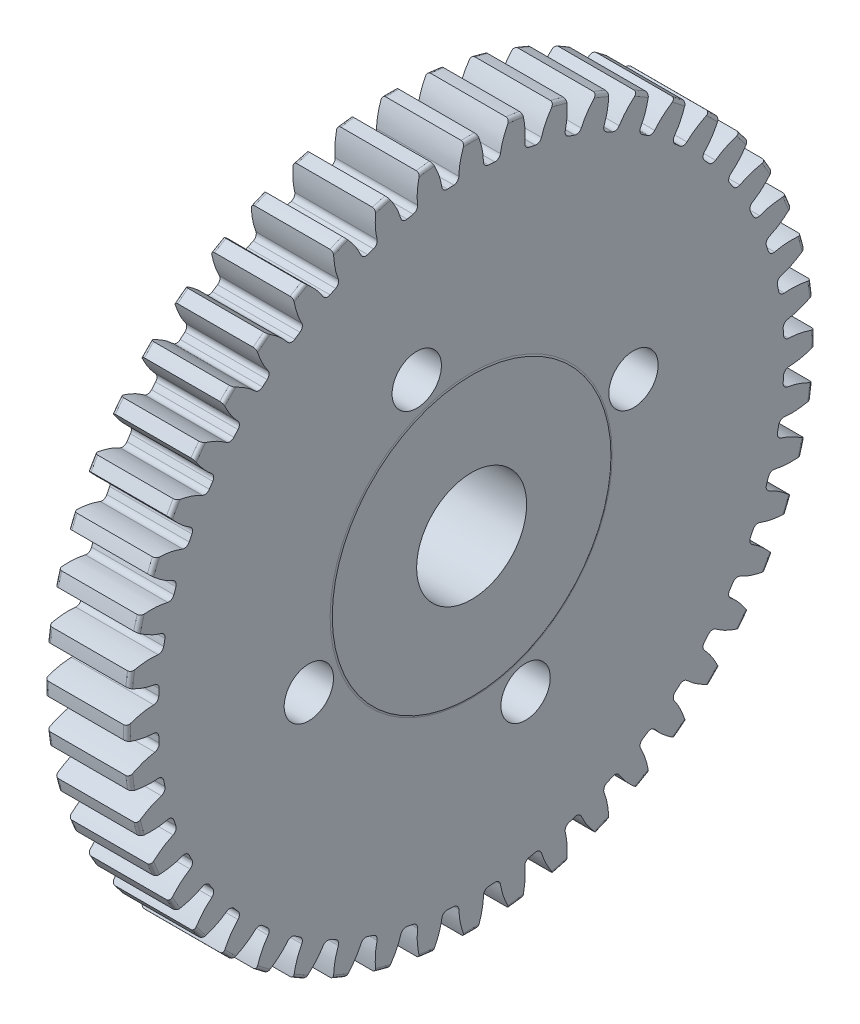
SolidWorks part; units mm, degrees
material "Delrin 2700 NC010, Low Viscosity Acetal Copolymer (SS)"
ref_plane "Front Plane" through (0, 0, 0) normal (0, 0, 1) x (1, 0, 0)
ref_plane "Top Plane" through (0, 0, 0) normal (0, 1, 0) x (1, 0, 0)
ref_plane "Right Plane" through (0, 0, 0) normal (1, 0, 0) x (0, 0, -1)
sketch "Sketch1" plane through (0, 0, 0) normal (0, 0, 1) x (1, 0, 0)
  line L0 (-2.3749, 19.8438) -> (-2.3749, 0)
  line L1 (-2.3749, 0) -> (2.3749, 0)
  line L2 (2.3749, 0) -> (2.3749, 19.8438)
  line L3 (2.3749, 19.8438) -> (-2.3749, 19.8438)
  line L4 (-2.3749, 0) -> (2.3749, 0) construction
revolve "Revolve1" add sketch "Sketch1" angle 360 about L4 reverse direction yes
sketch "Sketch2" plane through (-2.3749, 0, 0) normal (-1, 0, 0) x (0, 0, 1)
  arc A0 (0.7316, 18.0319) -> (1.6283, 17.9731) centre (0, 0) cw
  arc A1 (2.2123, 19.72) -> (0.3806, 19.8401) centre (0, 0) ccw
  spline S0 degree 3 poles (0.3806, 19.8401) (0.4054, 19.7738) (0.4294, 19.7071) (0.4523, 19.6401) (0.5249, 19.4282) (0.5865, 19.212) (0.6329, 18.9928) (0.6803, 18.7688) (0.6967, 18.5388) (0.7099, 18.3101) (0.7153, 18.2172) (0.7242, 18.1246) (0.7316, 18.0319) knots -0.000212 -0.000212 -0.000212 -0.000212 0 0 0 0.000672 0.000672 0.000672 0.001361 0.001361 0.001361 0.00164 0.00164 0.00164 0.00164
  spline S1 degree 3 poles (1.6283, 17.9731) (1.6477, 18.0641) (1.6686, 18.1548) (1.6861, 18.2461) (1.7281, 18.4663) (1.7727, 18.6874) (1.8467, 18.8989) (1.9223, 19.115) (2.0133, 19.326) (2.1151, 19.5311) (2.1466, 19.5946) (2.179, 19.6575) (2.2123, 19.72) knots -0.000279 -0.000279 -0.000279 -0.000279 0 0 0 0.000672 0.000672 0.000672 0.001357 0.001357 0.001357 0.001569 0.001569 0.001569 0.001569
extrude "Cut-Extrude1" cut sketch "Sketch2" against normal through all
sketch "Sketch3" plane through (-2.3749, 0, 0) normal (-1, 0, 0) x (0, 0, 1)
  arc A0 (3.079, 17.7821) -> (3.9603, 17.6068) centre (0, 0) cw
  arc A1 (4.7674, 19.2626) -> (2.967, 19.6207) centre (0, 0) ccw
  spline S0 degree 3 poles (2.967, 19.6207) (2.983, 19.5517) (2.998, 19.4825) (3.012, 19.413) (3.0562, 19.1935) (3.0891, 18.9711) (3.1065, 18.7477) (3.1243, 18.5194) (3.1106, 18.2892) (3.0938, 18.0608) (3.087, 17.968) (3.0838, 17.875) (3.079, 17.7821) knots -0.000212 -0.000212 -0.000212 -0.000212 0 0 0 0.000672 0.000672 0.000672 0.001361 0.001361 0.001361 0.00164 0.00164 0.00164 0.00164
  spline S1 degree 3 poles (3.9603, 17.6068) (3.9914, 17.6945) (4.024, 17.7816) (4.0533, 17.87) (4.1236, 18.0827) (4.1967, 18.2962) (4.2977, 18.4962) (4.4008, 18.7006) (4.5187, 18.8979) (4.6463, 19.088) (4.6858, 19.1467) (4.7262, 19.2049) (4.7674, 19.2626) knots -0.000279 -0.000279 -0.000279 -0.000279 0 0 0 0.000672 0.000672 0.000672 0.001357 0.001357 0.001357 0.001569 0.001569 0.001569 0.001569
extrude "Cut-Extrude2" cut sketch "Sketch3" against normal through all
sketch "Sketch4" plane through (-2.3749, 0, 0) normal (-1, 0, 0) x (0, 0, 1)
  arc A0 (5.3737, 17.2281) -> (6.2246, 16.9392) centre (0, 0) cw
  arc A1 (7.2408, 18.4755) -> (5.5026, 19.0656) centre (0, 0) ccw
  spline S0 degree 3 poles (5.5026, 19.0656) (5.5094, 18.9951) (5.5153, 18.9245) (5.5201, 18.8538) (5.5354, 18.6303) (5.5389, 18.4055) (5.527, 18.1819) (5.5148, 17.9532) (5.4712, 17.7267) (5.4248, 17.5025) (5.4059, 17.4114) (5.3906, 17.3196) (5.3737, 17.2281) knots -0.000212 -0.000212 -0.000212 -0.000212 0 0 0 0.000672 0.000672 0.000672 0.001361 0.001361 0.001361 0.00164 0.00164 0.00164 0.00164
  spline S1 degree 3 poles (6.2246, 16.9392) (6.2669, 17.0221) (6.3106, 17.1043) (6.3511, 17.188) (6.4486, 17.3898) (6.5489, 17.5918) (6.6752, 17.777) (6.8041, 17.9662) (6.9467, 18.1464) (7.0981, 18.3182) (7.1449, 18.3713) (7.1925, 18.4237) (7.2408, 18.4755) knots -0.000279 -0.000279 -0.000279 -0.000279 0 0 0 0.000672 0.000672 0.000672 0.001357 0.001357 0.001357 0.001569 0.001569 0.001569 0.001569
extrude "Cut-Extrude3" cut sketch "Sketch4" against normal through all
sketch "Sketch5" plane through (-2.3749, 0, 0) normal (-1, 0, 0) x (0, 0, 1)
  arc A0 (7.5764, 16.3793) -> (8.3824, 15.9819) centre (0, 0) cw
  arc A1 (9.5904, 17.3723) -> (7.9441, 18.1842) centre (0, 0) ccw
  spline S0 degree 3 poles (7.9441, 18.1842) (7.9417, 18.1134) (7.9383, 18.0427) (7.9338, 17.972) (7.9197, 17.7484) (7.894, 17.5251) (7.8529, 17.3049) (7.811, 17.0798) (7.7382, 16.8609) (7.6629, 16.6447) (7.6323, 16.5568) (7.6051, 16.4678) (7.5764, 16.3793) knots -0.000212 -0.000212 -0.000212 -0.000212 0 0 0 0.000672 0.000672 0.000672 0.001361 0.001361 0.001361 0.00164 0.00164 0.00164 0.00164
  spline S1 degree 3 poles (8.3824, 15.9819) (8.4351, 16.0585) (8.4892, 16.1342) (8.5402, 16.212) (8.6633, 16.3993) (8.7891, 16.5865) (8.9384, 16.7536) (9.091, 16.9244) (9.2558, 17.0845) (9.4283, 17.235) (9.4817, 17.2816) (9.5358, 17.3273) (9.5904, 17.3723) knots -0.000279 -0.000279 -0.000279 -0.000279 0 0 0 0.000672 0.000672 0.000672 0.001357 0.001357 0.001357 0.001569 0.001569 0.001569 0.001569
extrude "Cut-Extrude4" cut sketch "Sketch5" against normal through all
sketch "Sketch6" plane through (-2.3749, 0, 0) normal (-1, 0, 0) x (0, 0, 1)
  arc A0 (9.6495, 15.2503) -> (10.3967, 14.751) centre (0, 0) cw
  arc A1 (11.7759, 15.9719) -> (10.2497, 16.9917) centre (0, 0) ccw
  spline S0 degree 3 poles (10.2497, 16.9917) (10.238, 16.9219) (10.2254, 16.8522) (10.2118, 16.7827) (10.1686, 16.5629) (10.1139, 16.3448) (10.0445, 16.1318) (9.9735, 15.9141) (9.8728, 15.7067) (9.7699, 15.5021) (9.7281, 15.4189) (9.6895, 15.3342) (9.6495, 15.2503) knots -0.000212 -0.000212 -0.000212 -0.000212 0 0 0 0.000672 0.000672 0.000672 0.001361 0.001361 0.001361 0.00164 0.00164 0.00164 0.00164
  spline S1 degree 3 poles (10.3967, 14.751) (10.459, 14.8201) (10.5225, 14.8882) (10.5833, 14.9586) (10.7297, 15.1282) (10.8789, 15.2974) (11.0487, 15.4436) (11.2223, 15.593) (11.4066, 15.7302) (11.5973, 15.8569) (11.6563, 15.8961) (11.7159, 15.9344) (11.7759, 15.9719) knots -0.000279 -0.000279 -0.000279 -0.000279 0 0 0 0.000672 0.000672 0.000672 0.001357 0.001357 0.001357 0.001569 0.001569 0.001569 0.001569
extrude "Cut-Extrude5" cut sketch "Sketch6" against normal through all
sketch "Sketch7" plane through (-2.3749, 0, 0) normal (-1, 0, 0) x (0, 0, 1)
  arc A0 (11.5575, 13.8603) -> (12.2331, 13.2678) centre (0, 0) cw
  arc A1 (13.7599, 14.2982) -> (12.3798, 15.5085) centre (0, 0) ccw
  spline S0 degree 3 poles (12.3798, 15.5085) (12.3592, 15.4408) (12.3376, 15.3733) (12.315, 15.3062) (12.2435, 15.0939) (12.1608, 14.8848) (12.0642, 14.6828) (11.9654, 14.4761) (11.8384, 14.2836) (11.7097, 14.0942) (11.6574, 14.0173) (11.6081, 13.9383) (11.5575, 13.8603) knots -0.000212 -0.000212 -0.000212 -0.000212 0 0 0 0.000672 0.000672 0.000672 0.001361 0.001361 0.001361 0.00164 0.00164 0.00164 0.00164
  spline S1 degree 3 poles (12.2331, 13.2678) (12.3039, 13.3282) (12.3757, 13.3873) (12.4452, 13.4492) (12.6125, 13.5983) (12.7825, 13.7466) (12.97, 13.8693) (13.1615, 13.9948) (13.3622, 14.1067) (13.5678, 14.2075) (13.6314, 14.2387) (13.6955, 14.2689) (13.7599, 14.2982) knots -0.000279 -0.000279 -0.000279 -0.000279 0 0 0 0.000672 0.000672 0.000672 0.001357 0.001357 0.001357 0.001569 0.001569 0.001569 0.001569
extrude "Cut-Extrude6" cut sketch "Sketch7" against normal through all
sketch "Sketch8" plane through (-2.3749, 0, 0) normal (-1, 0, 0) x (0, 0, 1)
  arc A0 (13.2678, 12.2331) -> (13.8603, 11.5575) centre (0, 0) cw
  arc A1 (15.5085, 12.3798) -> (14.2982, 13.7599) centre (0, 0) ccw
  spline S0 degree 3 poles (14.2982, 13.7599) (14.2689, 13.6955) (14.2387, 13.6314) (14.2075, 13.5678) (14.1089, 13.3667) (13.9996, 13.1702) (13.8775, 12.9824) (13.7526, 12.7905) (13.6016, 12.6162) (13.4492, 12.4452) (13.3873, 12.3757) (13.3282, 12.3039) (13.2678, 12.2331) knots -0.000212 -0.000212 -0.000212 -0.000212 0 0 0 0.000672 0.000672 0.000672 0.001361 0.001361 0.001361 0.00164 0.00164 0.00164 0.00164
  spline S1 degree 3 poles (13.8603, 11.5575) (13.9383, 11.6081) (14.0173, 11.6574) (14.0942, 11.7097) (14.2796, 11.8357) (14.4675, 11.9605) (14.6694, 12.0578) (14.8756, 12.1571) (15.0892, 12.2419) (15.3062, 12.315) (15.3733, 12.3376) (15.4408, 12.3592) (15.5085, 12.3798) knots -0.000279 -0.000279 -0.000279 -0.000279 0 0 0 0.000672 0.000672 0.000672 0.001357 0.001357 0.001357 0.001569 0.001569 0.001569 0.001569
extrude "Cut-Extrude7" cut sketch "Sketch8" against normal through all
sketch "Sketch9" plane through (-2.3749, 0, 0) normal (-1, 0, 0) x (0, 0, 1)
  arc A0 (14.751, 10.3967) -> (15.2503, 9.6495) centre (0, 0) cw
  arc A1 (16.9917, 10.2497) -> (15.9719, 11.7759) centre (0, 0) ccw
  spline S0 degree 3 poles (15.9719, 11.7759) (15.9344, 11.7159) (15.8961, 11.6563) (15.8569, 11.5973) (15.7329, 11.4107) (15.5989, 11.2302) (15.4533, 11.06) (15.3044, 10.886) (15.1319, 10.7329) (14.9586, 10.5833) (14.8882, 10.5225) (14.8201, 10.459) (14.751, 10.3967) knots -0.000212 -0.000212 -0.000212 -0.000212 0 0 0 0.000672 0.000672 0.000672 0.001361 0.001361 0.001361 0.00164 0.00164 0.00164 0.00164
  spline S1 degree 3 poles (15.2503, 9.6495) (15.3342, 9.6895) (15.4189, 9.7281) (15.5021, 9.7699) (15.7023, 9.8706) (15.9049, 9.9698) (16.1177, 10.0399) (16.3352, 10.1114) (16.558, 10.1677) (16.7827, 10.2118) (16.8522, 10.2254) (16.9219, 10.238) (16.9917, 10.2497) knots -0.000279 -0.000279 -0.000279 -0.000279 0 0 0 0.000672 0.000672 0.000672 0.001357 0.001357 0.001357 0.001569 0.001569 0.001569 0.001569
extrude "Cut-Extrude8" cut sketch "Sketch9" against normal through all
sketch "Sketch10" plane through (-2.3749, 0, 0) normal (-1, 0, 0) x (0, 0, 1)
  arc A0 (15.9819, 8.3824) -> (16.3793, 7.5764) centre (0, 0) cw
  arc A1 (18.1842, 7.9441) -> (17.3723, 9.5904) centre (0, 0) ccw
  spline S0 degree 3 poles (17.3723, 9.5904) (17.3273, 9.5358) (17.2816, 9.4817) (17.235, 9.4283) (17.0877, 9.2596) (16.9313, 9.0981) (16.7647, 8.9483) (16.5944, 8.7953) (16.4034, 8.666) (16.212, 8.5402) (16.1342, 8.4892) (16.0585, 8.4351) (15.9819, 8.3824) knots -0.000212 -0.000212 -0.000212 -0.000212 0 0 0 0.000672 0.000672 0.000672 0.001361 0.001361 0.001361 0.00164 0.00164 0.00164 0.00164
  spline S1 degree 3 poles (16.3793, 7.5764) (16.4678, 7.6051) (16.5568, 7.6323) (16.6447, 7.6629) (16.8563, 7.7366) (17.0701, 7.8085) (17.2903, 7.8502) (17.5152, 7.8928) (17.7435, 7.9194) (17.972, 7.9338) (18.0427, 7.9383) (18.1134, 7.9417) (18.1842, 7.9441) knots -0.000279 -0.000279 -0.000279 -0.000279 0 0 0 0.000672 0.000672 0.000672 0.001357 0.001357 0.001357 0.001569 0.001569 0.001569 0.001569
extrude "Cut-Extrude9" cut sketch "Sketch10" against normal through all
sketch "Sketch11" plane through (-2.3749, 0, 0) normal (-1, 0, 0) x (0, 0, 1)
  arc A0 (16.9392, 6.2246) -> (17.2281, 5.3737) centre (0, 0) cw
  arc A1 (19.0656, 5.5026) -> (18.4755, 7.2408) centre (0, 0) ccw
  spline S0 degree 3 poles (18.4755, 7.2408) (18.4237, 7.1925) (18.3713, 7.1449) (18.3182, 7.0981) (18.1501, 6.9499) (17.974, 6.8102) (17.7893, 6.6835) (17.6004, 6.554) (17.3942, 6.4508) (17.188, 6.3511) (17.1043, 6.3106) (17.0221, 6.2669) (16.9392, 6.2246) knots -0.000212 -0.000212 -0.000212 -0.000212 0 0 0 0.000672 0.000672 0.000672 0.001361 0.001361 0.001361 0.00164 0.00164 0.00164 0.00164
  spline S1 degree 3 poles (17.2281, 5.3737) (17.3196, 5.3906) (17.4114, 5.4059) (17.5025, 5.4248) (17.7219, 5.4702) (17.9433, 5.5136) (18.167, 5.5262) (18.3956, 5.539) (18.6254, 5.5357) (18.8538, 5.5201) (18.9245, 5.5153) (18.9951, 5.5094) (19.0656, 5.5026) knots -0.000279 -0.000279 -0.000279 -0.000279 0 0 0 0.000672 0.000672 0.000672 0.001357 0.001357 0.001357 0.001569 0.001569 0.001569 0.001569
extrude "Cut-Extrude10" cut sketch "Sketch11" against normal through all
sketch "Sketch12" plane through (-2.3749, 0, 0) normal (-1, 0, 0) x (0, 0, 1)
  arc A0 (17.6068, 3.9603) -> (17.7821, 3.079) centre (0, 0) cw
  arc A1 (19.6207, 2.967) -> (19.2626, 4.7674) centre (0, 0) ccw
  spline S0 degree 3 poles (19.2626, 4.7674) (19.2049, 4.7262) (19.1467, 4.6858) (19.088, 4.6463) (18.902, 4.5214) (18.7091, 4.4059) (18.5095, 4.3044) (18.3053, 4.2006) (18.0874, 4.1252) (17.87, 4.0533) (17.7816, 4.024) (17.6945, 3.9914) (17.6068, 3.9603) knots -0.000212 -0.000212 -0.000212 -0.000212 0 0 0 0.000672 0.000672 0.000672 0.001361 0.001361 0.001361 0.00164 0.00164 0.00164 0.00164
  spline S1 degree 3 poles (17.7821, 3.079) (17.875, 3.0838) (17.968, 3.087) (18.0608, 3.0938) (18.2843, 3.1102) (18.5095, 3.1244) (18.7329, 3.1076) (18.9612, 3.0906) (19.1886, 3.0572) (19.413, 3.012) (19.4825, 2.998) (19.5517, 2.983) (19.6207, 2.967) knots -0.000279 -0.000279 -0.000279 -0.000279 0 0 0 0.000672 0.000672 0.000672 0.001357 0.001357 0.001357 0.001569 0.001569 0.001569 0.001569
extrude "Cut-Extrude11" cut sketch "Sketch12" against normal through all
sketch "Sketch13" plane through (-2.3749, 0, 0) normal (-1, 0, 0) x (0, 0, 1)
  arc A0 (17.9731, 1.6283) -> (18.0319, 0.7316) centre (0, 0) cw
  arc A1 (19.8401, 0.3806) -> (19.72, 2.2123) centre (0, 0) ccw
  spline S0 degree 3 poles (19.72, 2.2123) (19.6575, 2.179) (19.5946, 2.1466) (19.5311, 2.1151) (19.3305, 2.0155) (19.1242, 1.9262) (18.9129, 1.8516) (18.697, 1.7754) (18.4711, 1.729) (18.2461, 1.6861) (18.1548, 1.6686) (18.0641, 1.6477) (17.9731, 1.6283) knots -0.000212 -0.000212 -0.000212 -0.000212 0 0 0 0.000672 0.000672 0.000672 0.001361 0.001361 0.001361 0.00164 0.00164 0.00164 0.00164
  spline S1 degree 3 poles (18.0319, 0.7316) (18.1246, 0.7243) (18.2172, 0.7153) (18.3101, 0.7099) (18.5338, 0.697) (18.7589, 0.6817) (18.9783, 0.6359) (19.2024, 0.5892) (19.4235, 0.5265) (19.6401, 0.4523) (19.7071, 0.4294) (19.7738, 0.4054) (19.8401, 0.3806) knots -0.000279 -0.000279 -0.000279 -0.000279 0 0 0 0.000672 0.000672 0.000672 0.001357 0.001357 0.001357 0.001569 0.001569 0.001569 0.001569
extrude "Cut-Extrude12" cut sketch "Sketch13" against normal through all
sketch "Sketch14" plane through (-2.3749, 0, 0) normal (-1, 0, 0) x (0, 0, 1)
  arc A0 (18.0319, -0.7316) -> (17.9731, -1.6283) centre (0, 0) cw
  arc A1 (19.72, -2.2123) -> (19.8401, -0.3806) centre (0, 0) ccw
  spline S0 degree 3 poles (19.8401, -0.3806) (19.7738, -0.4054) (19.7071, -0.4294) (19.6401, -0.4523) (19.4282, -0.5249) (19.212, -0.5865) (18.9928, -0.6329) (18.7688, -0.6803) (18.5388, -0.6967) (18.3101, -0.7099) (18.2172, -0.7153) (18.1246, -0.7242) (18.0319, -0.7316) knots -0.000212 -0.000212 -0.000212 -0.000212 0 0 0 0.000672 0.000672 0.000672 0.001361 0.001361 0.001361 0.00164 0.00164 0.00164 0.00164
  spline S1 degree 3 poles (17.9731, -1.6283) (18.0641, -1.6477) (18.1548, -1.6686) (18.2461, -1.6861) (18.4663, -1.7281) (18.6874, -1.7727) (18.8989, -1.8467) (19.115, -1.9223) (19.326, -2.0133) (19.5311, -2.1151) (19.5946, -2.1466) (19.6575, -2.179) (19.72, -2.2123) knots -0.000279 -0.000279 -0.000279 -0.000279 0 0 0 0.000672 0.000672 0.000672 0.001357 0.001357 0.001357 0.001569 0.001569 0.001569 0.001569
extrude "Cut-Extrude13" cut sketch "Sketch14" against normal through all
sketch "Sketch15" plane through (-2.3749, 0, 0) normal (-1, 0, 0) x (0, 0, 1)
  arc A0 (17.7821, -3.079) -> (17.6068, -3.9603) centre (0, 0) cw
  arc A1 (19.2626, -4.7674) -> (19.6207, -2.967) centre (0, 0) ccw
  spline S0 degree 3 poles (19.6207, -2.967) (19.5517, -2.983) (19.4825, -2.998) (19.413, -3.012) (19.1935, -3.0562) (18.9711, -3.0891) (18.7477, -3.1065) (18.5194, -3.1243) (18.2892, -3.1106) (18.0608, -3.0938) (17.968, -3.087) (17.875, -3.0838) (17.7821, -3.079) knots -0.000212 -0.000212 -0.000212 -0.000212 0 0 0 0.000672 0.000672 0.000672 0.001361 0.001361 0.001361 0.00164 0.00164 0.00164 0.00164
  spline S1 degree 3 poles (17.6068, -3.9603) (17.6945, -3.9914) (17.7816, -4.024) (17.87, -4.0533) (18.0827, -4.1236) (18.2962, -4.1967) (18.4962, -4.2977) (18.7006, -4.4008) (18.8979, -4.5187) (19.088, -4.6463) (19.1467, -4.6858) (19.2049, -4.7262) (19.2626, -4.7674) knots -0.000279 -0.000279 -0.000279 -0.000279 0 0 0 0.000672 0.000672 0.000672 0.001357 0.001357 0.001357 0.001569 0.001569 0.001569 0.001569
extrude "Cut-Extrude14" cut sketch "Sketch15" against normal through all
sketch "Sketch16" plane through (-2.3749, 0, 0) normal (-1, 0, 0) x (0, 0, 1)
  arc A0 (17.2281, -5.3737) -> (16.9392, -6.2246) centre (0, 0) cw
  arc A1 (18.4755, -7.2408) -> (19.0656, -5.5026) centre (0, 0) ccw
  spline S0 degree 3 poles (19.0656, -5.5026) (18.9951, -5.5094) (18.9245, -5.5153) (18.8538, -5.5201) (18.6303, -5.5354) (18.4055, -5.5389) (18.1819, -5.527) (17.9532, -5.5148) (17.7267, -5.4712) (17.5025, -5.4248) (17.4114, -5.4059) (17.3196, -5.3906) (17.2281, -5.3737) knots -0.000212 -0.000212 -0.000212 -0.000212 0 0 0 0.000672 0.000672 0.000672 0.001361 0.001361 0.001361 0.00164 0.00164 0.00164 0.00164
  spline S1 degree 3 poles (16.9392, -6.2246) (17.0221, -6.2669) (17.1043, -6.3106) (17.188, -6.3511) (17.3898, -6.4486) (17.5918, -6.5489) (17.777, -6.6752) (17.9662, -6.8041) (18.1464, -6.9467) (18.3182, -7.0981) (18.3713, -7.1449) (18.4237, -7.1925) (18.4755, -7.2408) knots -0.000279 -0.000279 -0.000279 -0.000279 0 0 0 0.000672 0.000672 0.000672 0.001357 0.001357 0.001357 0.001569 0.001569 0.001569 0.001569
extrude "Cut-Extrude15" cut sketch "Sketch16" against normal through all
sketch "Sketch17" plane through (-2.3749, 0, 0) normal (-1, 0, 0) x (0, 0, 1)
  arc A0 (16.3793, -7.5764) -> (15.9819, -8.3824) centre (0, 0) cw
  arc A1 (17.3723, -9.5904) -> (18.1842, -7.9441) centre (0, 0) ccw
  spline S0 degree 3 poles (18.1842, -7.9441) (18.1134, -7.9417) (18.0427, -7.9383) (17.972, -7.9338) (17.7484, -7.9197) (17.5251, -7.894) (17.3049, -7.8529) (17.0798, -7.811) (16.8609, -7.7382) (16.6447, -7.6629) (16.5568, -7.6323) (16.4678, -7.6051) (16.3793, -7.5764) knots -0.000212 -0.000212 -0.000212 -0.000212 0 0 0 0.000672 0.000672 0.000672 0.001361 0.001361 0.001361 0.00164 0.00164 0.00164 0.00164
  spline S1 degree 3 poles (15.9819, -8.3824) (16.0585, -8.4351) (16.1342, -8.4892) (16.212, -8.5402) (16.3993, -8.6633) (16.5865, -8.7891) (16.7536, -8.9384) (16.9244, -9.091) (17.0845, -9.2558) (17.235, -9.4283) (17.2816, -9.4817) (17.3273, -9.5358) (17.3723, -9.5904) knots -0.000279 -0.000279 -0.000279 -0.000279 0 0 0 0.000672 0.000672 0.000672 0.001357 0.001357 0.001357 0.001569 0.001569 0.001569 0.001569
extrude "Cut-Extrude16" cut sketch "Sketch17" against normal through all
sketch "Sketch18" plane through (-2.3749, 0, 0) normal (-1, 0, 0) x (0, 0, 1)
  arc A0 (15.2503, -9.6495) -> (14.751, -10.3967) centre (0, 0) cw
  arc A1 (15.9719, -11.7759) -> (16.9917, -10.2497) centre (0, 0) ccw
  spline S0 degree 3 poles (16.9917, -10.2497) (16.9219, -10.238) (16.8522, -10.2254) (16.7827, -10.2118) (16.5629, -10.1686) (16.3448, -10.1139) (16.1318, -10.0445) (15.9141, -9.9735) (15.7067, -9.8728) (15.5021, -9.7699) (15.4189, -9.7281) (15.3342, -9.6895) (15.2503, -9.6495) knots -0.000212 -0.000212 -0.000212 -0.000212 0 0 0 0.000672 0.000672 0.000672 0.001361 0.001361 0.001361 0.00164 0.00164 0.00164 0.00164
  spline S1 degree 3 poles (14.751, -10.3967) (14.8201, -10.459) (14.8882, -10.5225) (14.9586, -10.5833) (15.1282, -10.7297) (15.2974, -10.8789) (15.4436, -11.0487) (15.593, -11.2223) (15.7302, -11.4066) (15.8569, -11.5973) (15.8961, -11.6563) (15.9344, -11.7159) (15.9719, -11.7759) knots -0.000279 -0.000279 -0.000279 -0.000279 0 0 0 0.000672 0.000672 0.000672 0.001357 0.001357 0.001357 0.001569 0.001569 0.001569 0.001569
extrude "Cut-Extrude17" cut sketch "Sketch18" against normal through all
sketch "Sketch19" plane through (-2.3749, 0, 0) normal (-1, 0, 0) x (0, 0, 1)
  arc A0 (13.8603, -11.5575) -> (13.2678, -12.2331) centre (0, 0) cw
  arc A1 (14.2982, -13.7599) -> (15.5085, -12.3798) centre (0, 0) ccw
  spline S0 degree 3 poles (15.5085, -12.3798) (15.4408, -12.3592) (15.3733, -12.3376) (15.3062, -12.315) (15.0939, -12.2435) (14.8848, -12.1608) (14.6828, -12.0642) (14.4761, -11.9654) (14.2836, -11.8384) (14.0942, -11.7097) (14.0173, -11.6574) (13.9383, -11.6081) (13.8603, -11.5575) knots -0.000212 -0.000212 -0.000212 -0.000212 0 0 0 0.000672 0.000672 0.000672 0.001361 0.001361 0.001361 0.00164 0.00164 0.00164 0.00164
  spline S1 degree 3 poles (13.2678, -12.2331) (13.3282, -12.3039) (13.3873, -12.3757) (13.4492, -12.4452) (13.5983, -12.6125) (13.7466, -12.7825) (13.8693, -12.97) (13.9948, -13.1615) (14.1067, -13.3622) (14.2075, -13.5678) (14.2387, -13.6314) (14.2689, -13.6955) (14.2982, -13.7599) knots -0.000279 -0.000279 -0.000279 -0.000279 0 0 0 0.000672 0.000672 0.000672 0.001357 0.001357 0.001357 0.001569 0.001569 0.001569 0.001569
extrude "Cut-Extrude18" cut sketch "Sketch19" against normal through all
sketch "Sketch20" plane through (-2.3749, 0, 0) normal (-1, 0, 0) x (0, 0, 1)
  arc A0 (12.2331, -13.2678) -> (11.5575, -13.8603) centre (0, 0) cw
  arc A1 (12.3798, -15.5085) -> (13.7599, -14.2982) centre (0, 0) ccw
  spline S0 degree 3 poles (13.7599, -14.2982) (13.6955, -14.2689) (13.6314, -14.2387) (13.5678, -14.2075) (13.3667, -14.1089) (13.1702, -13.9996) (12.9824, -13.8775) (12.7905, -13.7526) (12.6162, -13.6016) (12.4452, -13.4492) (12.3757, -13.3873) (12.3039, -13.3282) (12.2331, -13.2678) knots -0.000212 -0.000212 -0.000212 -0.000212 0 0 0 0.000672 0.000672 0.000672 0.001361 0.001361 0.001361 0.00164 0.00164 0.00164 0.00164
  spline S1 degree 3 poles (11.5575, -13.8603) (11.6081, -13.9383) (11.6574, -14.0173) (11.7097, -14.0942) (11.8357, -14.2796) (11.9605, -14.4675) (12.0578, -14.6694) (12.1571, -14.8756) (12.2419, -15.0892) (12.315, -15.3062) (12.3376, -15.3733) (12.3592, -15.4408) (12.3798, -15.5085) knots -0.000279 -0.000279 -0.000279 -0.000279 0 0 0 0.000672 0.000672 0.000672 0.001357 0.001357 0.001357 0.001569 0.001569 0.001569 0.001569
extrude "Cut-Extrude19" cut sketch "Sketch20" against normal through all
sketch "Sketch21" plane through (-2.3749, 0, 0) normal (-1, 0, 0) x (0, 0, 1)
  arc A0 (10.3967, -14.751) -> (9.6495, -15.2503) centre (0, 0) cw
  arc A1 (10.2497, -16.9917) -> (11.7759, -15.9719) centre (0, 0) ccw
  spline S0 degree 3 poles (11.7759, -15.9719) (11.7159, -15.9344) (11.6563, -15.8961) (11.5973, -15.8569) (11.4107, -15.7329) (11.2302, -15.5989) (11.06, -15.4533) (10.886, -15.3044) (10.7329, -15.1319) (10.5833, -14.9586) (10.5225, -14.8882) (10.459, -14.8201) (10.3967, -14.751) knots -0.000212 -0.000212 -0.000212 -0.000212 0 0 0 0.000672 0.000672 0.000672 0.001361 0.001361 0.001361 0.00164 0.00164 0.00164 0.00164
  spline S1 degree 3 poles (9.6495, -15.2503) (9.6895, -15.3342) (9.7281, -15.4189) (9.7699, -15.5021) (9.8706, -15.7023) (9.9698, -15.9049) (10.0399, -16.1177) (10.1114, -16.3352) (10.1677, -16.558) (10.2118, -16.7827) (10.2254, -16.8522) (10.238, -16.9219) (10.2497, -16.9917) knots -0.000279 -0.000279 -0.000279 -0.000279 0 0 0 0.000672 0.000672 0.000672 0.001357 0.001357 0.001357 0.001569 0.001569 0.001569 0.001569
extrude "Cut-Extrude20" cut sketch "Sketch21" against normal through all
sketch "Sketch22" plane through (-2.3749, 0, 0) normal (-1, 0, 0) x (0, 0, 1)
  arc A0 (8.3824, -15.9819) -> (7.5764, -16.3793) centre (0, 0) cw
  arc A1 (7.9441, -18.1842) -> (9.5904, -17.3723) centre (0, 0) ccw
  spline S0 degree 3 poles (9.5904, -17.3723) (9.5358, -17.3273) (9.4817, -17.2816) (9.4283, -17.235) (9.2596, -17.0877) (9.0981, -16.9313) (8.9483, -16.7647) (8.7953, -16.5944) (8.666, -16.4034) (8.5402, -16.212) (8.4892, -16.1342) (8.4351, -16.0585) (8.3824, -15.9819) knots -0.000212 -0.000212 -0.000212 -0.000212 0 0 0 0.000672 0.000672 0.000672 0.001361 0.001361 0.001361 0.00164 0.00164 0.00164 0.00164
  spline S1 degree 3 poles (7.5764, -16.3793) (7.6051, -16.4678) (7.6323, -16.5568) (7.6629, -16.6447) (7.7366, -16.8563) (7.8085, -17.0701) (7.8502, -17.2903) (7.8928, -17.5152) (7.9194, -17.7435) (7.9338, -17.972) (7.9383, -18.0427) (7.9417, -18.1134) (7.9441, -18.1842) knots -0.000279 -0.000279 -0.000279 -0.000279 0 0 0 0.000672 0.000672 0.000672 0.001357 0.001357 0.001357 0.001569 0.001569 0.001569 0.001569
extrude "Cut-Extrude21" cut sketch "Sketch22" against normal through all
sketch "Sketch23" plane through (-2.3749, 0, 0) normal (-1, 0, 0) x (0, 0, 1)
  arc A0 (6.2246, -16.9392) -> (5.3737, -17.2281) centre (0, 0) cw
  arc A1 (5.5026, -19.0656) -> (7.2408, -18.4755) centre (0, 0) ccw
  spline S0 degree 3 poles (7.2408, -18.4755) (7.1925, -18.4237) (7.1449, -18.3713) (7.0981, -18.3182) (6.9499, -18.1501) (6.8102, -17.974) (6.6835, -17.7893) (6.554, -17.6004) (6.4508, -17.3942) (6.3511, -17.188) (6.3106, -17.1043) (6.2669, -17.0221) (6.2246, -16.9392) knots -0.000212 -0.000212 -0.000212 -0.000212 0 0 0 0.000672 0.000672 0.000672 0.001361 0.001361 0.001361 0.00164 0.00164 0.00164 0.00164
  spline S1 degree 3 poles (5.3737, -17.2281) (5.3906, -17.3196) (5.4059, -17.4114) (5.4248, -17.5025) (5.4702, -17.7219) (5.5136, -17.9433) (5.5262, -18.167) (5.539, -18.3956) (5.5357, -18.6254) (5.5201, -18.8538) (5.5153, -18.9245) (5.5094, -18.9951) (5.5026, -19.0656) knots -0.000279 -0.000279 -0.000279 -0.000279 0 0 0 0.000672 0.000672 0.000672 0.001357 0.001357 0.001357 0.001569 0.001569 0.001569 0.001569
extrude "Cut-Extrude22" cut sketch "Sketch23" against normal through all
sketch "Sketch24" plane through (-2.3749, 0, 0) normal (-1, 0, 0) x (0, 0, 1)
  arc A0 (3.9603, -17.6068) -> (3.079, -17.7821) centre (0, 0) cw
  arc A1 (2.967, -19.6207) -> (4.7674, -19.2626) centre (0, 0) ccw
  spline S0 degree 3 poles (4.7674, -19.2626) (4.7262, -19.2049) (4.6858, -19.1467) (4.6463, -19.088) (4.5214, -18.902) (4.4059, -18.7091) (4.3044, -18.5095) (4.2006, -18.3053) (4.1252, -18.0874) (4.0533, -17.87) (4.024, -17.7816) (3.9914, -17.6945) (3.9603, -17.6068) knots -0.000212 -0.000212 -0.000212 -0.000212 0 0 0 0.000672 0.000672 0.000672 0.001361 0.001361 0.001361 0.00164 0.00164 0.00164 0.00164
  spline S1 degree 3 poles (3.079, -17.7821) (3.0838, -17.875) (3.087, -17.968) (3.0938, -18.0608) (3.1102, -18.2843) (3.1244, -18.5095) (3.1076, -18.7329) (3.0906, -18.9612) (3.0572, -19.1886) (3.012, -19.413) (2.998, -19.4825) (2.983, -19.5517) (2.967, -19.6207) knots -0.000279 -0.000279 -0.000279 -0.000279 0 0 0 0.000672 0.000672 0.000672 0.001357 0.001357 0.001357 0.001569 0.001569 0.001569 0.001569
extrude "Cut-Extrude23" cut sketch "Sketch24" against normal through all
sketch "Sketch25" plane through (-2.3749, 0, 0) normal (-1, 0, 0) x (0, 0, 1)
  arc A0 (1.6283, -17.9731) -> (0.7316, -18.0319) centre (0, 0) cw
  arc A1 (0.3806, -19.8401) -> (2.2123, -19.72) centre (0, 0) ccw
  spline S0 degree 3 poles (2.2123, -19.72) (2.179, -19.6575) (2.1466, -19.5946) (2.1151, -19.5311) (2.0155, -19.3305) (1.9262, -19.1242) (1.8516, -18.9129) (1.7754, -18.697) (1.729, -18.4711) (1.6861, -18.2461) (1.6686, -18.1548) (1.6477, -18.0641) (1.6283, -17.9731) knots -0.000212 -0.000212 -0.000212 -0.000212 0 0 0 0.000672 0.000672 0.000672 0.001361 0.001361 0.001361 0.00164 0.00164 0.00164 0.00164
  spline S1 degree 3 poles (0.7316, -18.0319) (0.7243, -18.1246) (0.7153, -18.2172) (0.7099, -18.3101) (0.697, -18.5338) (0.6817, -18.7589) (0.6359, -18.9783) (0.5892, -19.2024) (0.5265, -19.4235) (0.4523, -19.6401) (0.4294, -19.7071) (0.4054, -19.7738) (0.3806, -19.8401) knots -0.000279 -0.000279 -0.000279 -0.000279 0 0 0 0.000672 0.000672 0.000672 0.001357 0.001357 0.001357 0.001569 0.001569 0.001569 0.001569
extrude "Cut-Extrude24" cut sketch "Sketch25" against normal through all
sketch "Sketch26" plane through (-2.3749, 0, 0) normal (-1, 0, 0) x (0, 0, 1)
  arc A0 (-2.2123, -19.72) -> (-0.3806, -19.8401) centre (0, 0) ccw
  arc A1 (-0.7316, -18.0319) -> (-1.6283, -17.9731) centre (0, 0) cw
  spline S0 degree 3 poles (-0.3806, -19.8401) (-0.4054, -19.7738) (-0.4294, -19.7071) (-0.4523, -19.6401) (-0.5249, -19.4282) (-0.5865, -19.212) (-0.6329, -18.9928) (-0.6803, -18.7688) (-0.6967, -18.5388) (-0.7099, -18.3101) (-0.7153, -18.2172) (-0.7242, -18.1246) (-0.7316, -18.0319) knots -0.000212 -0.000212 -0.000212 -0.000212 0 0 0 0.000672 0.000672 0.000672 0.001361 0.001361 0.001361 0.00164 0.00164 0.00164 0.00164
  spline S1 degree 3 poles (-1.6283, -17.9731) (-1.6477, -18.0641) (-1.6686, -18.1548) (-1.6861, -18.2461) (-1.7281, -18.4663) (-1.7727, -18.6874) (-1.8467, -18.8989) (-1.9223, -19.115) (-2.0133, -19.326) (-2.1151, -19.5311) (-2.1466, -19.5946) (-2.179, -19.6575) (-2.2123, -19.72) knots -0.000279 -0.000279 -0.000279 -0.000279 0 0 0 0.000672 0.000672 0.000672 0.001357 0.001357 0.001357 0.001569 0.001569 0.001569 0.001569
extrude "Cut-Extrude25" cut sketch "Sketch26" against normal through all
sketch "Sketch27" plane through (-2.3749, 0, 0) normal (-1, 0, 0) x (0, 0, 1)
  arc A0 (-4.7674, -19.2626) -> (-2.967, -19.6207) centre (0, 0) ccw
  arc A1 (-3.079, -17.7821) -> (-3.9603, -17.6068) centre (0, 0) cw
  spline S0 degree 3 poles (-2.967, -19.6207) (-2.983, -19.5517) (-2.998, -19.4825) (-3.012, -19.413) (-3.0562, -19.1935) (-3.0891, -18.9711) (-3.1065, -18.7477) (-3.1243, -18.5194) (-3.1106, -18.2892) (-3.0938, -18.0608) (-3.087, -17.968) (-3.0838, -17.875) (-3.079, -17.7821) knots -0.000212 -0.000212 -0.000212 -0.000212 0 0 0 0.000672 0.000672 0.000672 0.001361 0.001361 0.001361 0.00164 0.00164 0.00164 0.00164
  spline S1 degree 3 poles (-3.9603, -17.6068) (-3.9914, -17.6945) (-4.024, -17.7816) (-4.0533, -17.87) (-4.1236, -18.0827) (-4.1967, -18.2962) (-4.2977, -18.4962) (-4.4008, -18.7006) (-4.5187, -18.8979) (-4.6463, -19.088) (-4.6858, -19.1467) (-4.7262, -19.2049) (-4.7674, -19.2626) knots -0.000279 -0.000279 -0.000279 -0.000279 0 0 0 0.000672 0.000672 0.000672 0.001357 0.001357 0.001357 0.001569 0.001569 0.001569 0.001569
extrude "Cut-Extrude26" cut sketch "Sketch27" against normal through all
sketch "Sketch28" plane through (-2.3749, 0, 0) normal (-1, 0, 0) x (0, 0, 1)
  arc A0 (-7.2408, -18.4755) -> (-5.5026, -19.0656) centre (0, 0) ccw
  arc A1 (-5.3737, -17.2281) -> (-6.2246, -16.9392) centre (0, 0) cw
  spline S0 degree 3 poles (-5.5026, -19.0656) (-5.5094, -18.9951) (-5.5153, -18.9245) (-5.5201, -18.8538) (-5.5354, -18.6303) (-5.5389, -18.4055) (-5.527, -18.1819) (-5.5148, -17.9532) (-5.4712, -17.7267) (-5.4248, -17.5025) (-5.4059, -17.4114) (-5.3906, -17.3196) (-5.3737, -17.2281) knots -0.000212 -0.000212 -0.000212 -0.000212 0 0 0 0.000672 0.000672 0.000672 0.001361 0.001361 0.001361 0.00164 0.00164 0.00164 0.00164
  spline S1 degree 3 poles (-6.2246, -16.9392) (-6.2669, -17.0221) (-6.3106, -17.1043) (-6.3511, -17.188) (-6.4486, -17.3898) (-6.5489, -17.5918) (-6.6752, -17.777) (-6.8041, -17.9662) (-6.9467, -18.1464) (-7.0981, -18.3182) (-7.1449, -18.3713) (-7.1925, -18.4237) (-7.2408, -18.4755) knots -0.000279 -0.000279 -0.000279 -0.000279 0 0 0 0.000672 0.000672 0.000672 0.001357 0.001357 0.001357 0.001569 0.001569 0.001569 0.001569
extrude "Cut-Extrude27" cut sketch "Sketch28" against normal through all
sketch "Sketch29" plane through (-2.3749, 0, 0) normal (-1, 0, 0) x (0, 0, 1)
  arc A0 (-9.5904, -17.3723) -> (-7.9441, -18.1842) centre (0, 0) ccw
  arc A1 (-7.5764, -16.3793) -> (-8.3824, -15.9819) centre (0, 0) cw
  spline S0 degree 3 poles (-7.9441, -18.1842) (-7.9417, -18.1134) (-7.9383, -18.0427) (-7.9338, -17.972) (-7.9197, -17.7484) (-7.894, -17.5251) (-7.8529, -17.3049) (-7.811, -17.0798) (-7.7382, -16.8609) (-7.6629, -16.6447) (-7.6323, -16.5568) (-7.6051, -16.4678) (-7.5764, -16.3793) knots -0.000212 -0.000212 -0.000212 -0.000212 0 0 0 0.000672 0.000672 0.000672 0.001361 0.001361 0.001361 0.00164 0.00164 0.00164 0.00164
  spline S1 degree 3 poles (-8.3824, -15.9819) (-8.4351, -16.0585) (-8.4892, -16.1342) (-8.5402, -16.212) (-8.6633, -16.3993) (-8.7891, -16.5865) (-8.9384, -16.7536) (-9.091, -16.9244) (-9.2558, -17.0845) (-9.4283, -17.235) (-9.4817, -17.2816) (-9.5358, -17.3273) (-9.5904, -17.3723) knots -0.000279 -0.000279 -0.000279 -0.000279 0 0 0 0.000672 0.000672 0.000672 0.001357 0.001357 0.001357 0.001569 0.001569 0.001569 0.001569
extrude "Cut-Extrude28" cut sketch "Sketch29" against normal through all
sketch "Sketch30" plane through (-2.3749, 0, 0) normal (-1, 0, 0) x (0, 0, 1)
  arc A0 (-11.7759, -15.9719) -> (-10.2497, -16.9917) centre (0, 0) ccw
  arc A1 (-9.6495, -15.2503) -> (-10.3967, -14.751) centre (0, 0) cw
  spline S0 degree 3 poles (-10.2497, -16.9917) (-10.238, -16.9219) (-10.2254, -16.8522) (-10.2118, -16.7827) (-10.1686, -16.5629) (-10.1139, -16.3448) (-10.0445, -16.1318) (-9.9735, -15.9141) (-9.8728, -15.7067) (-9.7699, -15.5021) (-9.7281, -15.4189) (-9.6895, -15.3342) (-9.6495, -15.2503) knots -0.000212 -0.000212 -0.000212 -0.000212 0 0 0 0.000672 0.000672 0.000672 0.001361 0.001361 0.001361 0.00164 0.00164 0.00164 0.00164
  spline S1 degree 3 poles (-10.3967, -14.751) (-10.459, -14.8201) (-10.5225, -14.8882) (-10.5833, -14.9586) (-10.7297, -15.1282) (-10.8789, -15.2974) (-11.0487, -15.4436) (-11.2223, -15.593) (-11.4066, -15.7302) (-11.5973, -15.8569) (-11.6563, -15.8961) (-11.7159, -15.9344) (-11.7759, -15.9719) knots -0.000279 -0.000279 -0.000279 -0.000279 0 0 0 0.000672 0.000672 0.000672 0.001357 0.001357 0.001357 0.001569 0.001569 0.001569 0.001569
extrude "Cut-Extrude29" cut sketch "Sketch30" against normal through all
sketch "Sketch31" plane through (-2.3749, 0, 0) normal (-1, 0, 0) x (0, 0, 1)
  arc A0 (-13.7599, -14.2982) -> (-12.3798, -15.5085) centre (0, 0) ccw
  arc A1 (-11.5575, -13.8603) -> (-12.2331, -13.2678) centre (0, 0) cw
  spline S0 degree 3 poles (-12.3798, -15.5085) (-12.3592, -15.4408) (-12.3376, -15.3733) (-12.315, -15.3062) (-12.2435, -15.0939) (-12.1608, -14.8848) (-12.0642, -14.6828) (-11.9654, -14.4761) (-11.8384, -14.2836) (-11.7097, -14.0942) (-11.6574, -14.0173) (-11.6081, -13.9383) (-11.5575, -13.8603) knots -0.000212 -0.000212 -0.000212 -0.000212 0 0 0 0.000672 0.000672 0.000672 0.001361 0.001361 0.001361 0.00164 0.00164 0.00164 0.00164
  spline S1 degree 3 poles (-12.2331, -13.2678) (-12.3039, -13.3282) (-12.3757, -13.3873) (-12.4452, -13.4492) (-12.6125, -13.5983) (-12.7825, -13.7466) (-12.97, -13.8693) (-13.1615, -13.9948) (-13.3622, -14.1067) (-13.5678, -14.2075) (-13.6314, -14.2387) (-13.6955, -14.2689) (-13.7599, -14.2982) knots -0.000279 -0.000279 -0.000279 -0.000279 0 0 0 0.000672 0.000672 0.000672 0.001357 0.001357 0.001357 0.001569 0.001569 0.001569 0.001569
extrude "Cut-Extrude30" cut sketch "Sketch31" against normal through all
sketch "Sketch32" plane through (-2.3749, 0, 0) normal (-1, 0, 0) x (0, 0, 1)
  arc A0 (-15.5085, -12.3798) -> (-14.2982, -13.7599) centre (0, 0) ccw
  arc A1 (-13.2678, -12.2331) -> (-13.8603, -11.5575) centre (0, 0) cw
  spline S0 degree 3 poles (-14.2982, -13.7599) (-14.2689, -13.6955) (-14.2387, -13.6314) (-14.2075, -13.5678) (-14.1089, -13.3667) (-13.9996, -13.1702) (-13.8775, -12.9824) (-13.7526, -12.7905) (-13.6016, -12.6162) (-13.4492, -12.4452) (-13.3873, -12.3757) (-13.3282, -12.3039) (-13.2678, -12.2331) knots -0.000212 -0.000212 -0.000212 -0.000212 0 0 0 0.000672 0.000672 0.000672 0.001361 0.001361 0.001361 0.00164 0.00164 0.00164 0.00164
  spline S1 degree 3 poles (-13.8603, -11.5575) (-13.9383, -11.6081) (-14.0173, -11.6574) (-14.0942, -11.7097) (-14.2796, -11.8357) (-14.4675, -11.9605) (-14.6694, -12.0578) (-14.8756, -12.1571) (-15.0892, -12.2419) (-15.3062, -12.315) (-15.3733, -12.3376) (-15.4408, -12.3592) (-15.5085, -12.3798) knots -0.000279 -0.000279 -0.000279 -0.000279 0 0 0 0.000672 0.000672 0.000672 0.001357 0.001357 0.001357 0.001569 0.001569 0.001569 0.001569
extrude "Cut-Extrude31" cut sketch "Sketch32" against normal through all
sketch "Sketch33" plane through (-2.3749, 0, 0) normal (-1, 0, 0) x (0, 0, 1)
  arc A0 (-16.9917, -10.2497) -> (-15.9719, -11.7759) centre (0, 0) ccw
  arc A1 (-14.751, -10.3967) -> (-15.2503, -9.6495) centre (0, 0) cw
  spline S0 degree 3 poles (-15.9719, -11.7759) (-15.9344, -11.7159) (-15.8961, -11.6563) (-15.8569, -11.5973) (-15.7329, -11.4107) (-15.5989, -11.2302) (-15.4533, -11.06) (-15.3044, -10.886) (-15.1319, -10.7329) (-14.9586, -10.5833) (-14.8882, -10.5225) (-14.8201, -10.459) (-14.751, -10.3967) knots -0.000212 -0.000212 -0.000212 -0.000212 0 0 0 0.000672 0.000672 0.000672 0.001361 0.001361 0.001361 0.00164 0.00164 0.00164 0.00164
  spline S1 degree 3 poles (-15.2503, -9.6495) (-15.3342, -9.6895) (-15.4189, -9.7281) (-15.5021, -9.7699) (-15.7023, -9.8706) (-15.9049, -9.9698) (-16.1177, -10.0399) (-16.3352, -10.1114) (-16.558, -10.1677) (-16.7827, -10.2118) (-16.8522, -10.2254) (-16.9219, -10.238) (-16.9917, -10.2497) knots -0.000279 -0.000279 -0.000279 -0.000279 0 0 0 0.000672 0.000672 0.000672 0.001357 0.001357 0.001357 0.001569 0.001569 0.001569 0.001569
extrude "Cut-Extrude32" cut sketch "Sketch33" against normal through all
sketch "Sketch34" plane through (-2.3749, 0, 0) normal (-1, 0, 0) x (0, 0, 1)
  arc A0 (-18.1842, -7.9441) -> (-17.3723, -9.5904) centre (0, 0) ccw
  arc A1 (-15.9819, -8.3824) -> (-16.3793, -7.5764) centre (0, 0) cw
  spline S0 degree 3 poles (-17.3723, -9.5904) (-17.3273, -9.5358) (-17.2816, -9.4817) (-17.235, -9.4283) (-17.0877, -9.2596) (-16.9313, -9.0981) (-16.7647, -8.9483) (-16.5944, -8.7953) (-16.4034, -8.666) (-16.212, -8.5402) (-16.1342, -8.4892) (-16.0585, -8.4351) (-15.9819, -8.3824) knots -0.000212 -0.000212 -0.000212 -0.000212 0 0 0 0.000672 0.000672 0.000672 0.001361 0.001361 0.001361 0.00164 0.00164 0.00164 0.00164
  spline S1 degree 3 poles (-16.3793, -7.5764) (-16.4678, -7.6051) (-16.5568, -7.6323) (-16.6447, -7.6629) (-16.8563, -7.7366) (-17.0701, -7.8085) (-17.2903, -7.8502) (-17.5152, -7.8928) (-17.7435, -7.9194) (-17.972, -7.9338) (-18.0427, -7.9383) (-18.1134, -7.9417) (-18.1842, -7.9441) knots -0.000279 -0.000279 -0.000279 -0.000279 0 0 0 0.000672 0.000672 0.000672 0.001357 0.001357 0.001357 0.001569 0.001569 0.001569 0.001569
extrude "Cut-Extrude33" cut sketch "Sketch34" against normal through all
sketch "Sketch35" plane through (-2.3749, 0, 0) normal (-1, 0, 0) x (0, 0, 1)
  arc A0 (-16.9392, -6.2246) -> (-17.2281, -5.3737) centre (0, 0) cw
  arc A1 (-19.0656, -5.5026) -> (-18.4755, -7.2408) centre (0, 0) ccw
  spline S0 degree 3 poles (-18.4755, -7.2408) (-18.4237, -7.1925) (-18.3713, -7.1449) (-18.3182, -7.0981) (-18.1501, -6.9499) (-17.974, -6.8102) (-17.7893, -6.6835) (-17.6004, -6.554) (-17.3942, -6.4508) (-17.188, -6.3511) (-17.1043, -6.3106) (-17.0221, -6.2669) (-16.9392, -6.2246) knots -0.000212 -0.000212 -0.000212 -0.000212 0 0 0 0.000672 0.000672 0.000672 0.001361 0.001361 0.001361 0.00164 0.00164 0.00164 0.00164
  spline S1 degree 3 poles (-17.2281, -5.3737) (-17.3196, -5.3906) (-17.4114, -5.4059) (-17.5025, -5.4248) (-17.7219, -5.4702) (-17.9433, -5.5136) (-18.167, -5.5262) (-18.3956, -5.539) (-18.6254, -5.5357) (-18.8538, -5.5201) (-18.9245, -5.5153) (-18.9951, -5.5094) (-19.0656, -5.5026) knots -0.000279 -0.000279 -0.000279 -0.000279 0 0 0 0.000672 0.000672 0.000672 0.001357 0.001357 0.001357 0.001569 0.001569 0.001569 0.001569
extrude "Cut-Extrude34" cut sketch "Sketch35" against normal through all
sketch "Sketch36" plane through (-2.3749, 0, 0) normal (-1, 0, 0) x (0, 0, 1)
  arc A0 (-17.6068, -3.9603) -> (-17.7821, -3.079) centre (0, 0) cw
  arc A1 (-19.6207, -2.967) -> (-19.2626, -4.7674) centre (0, 0) ccw
  spline S0 degree 3 poles (-19.2626, -4.7674) (-19.2049, -4.7262) (-19.1467, -4.6858) (-19.088, -4.6463) (-18.902, -4.5214) (-18.7091, -4.4059) (-18.5095, -4.3044) (-18.3053, -4.2006) (-18.0874, -4.1252) (-17.87, -4.0533) (-17.7816, -4.024) (-17.6945, -3.9914) (-17.6068, -3.9603) knots -0.000212 -0.000212 -0.000212 -0.000212 0 0 0 0.000672 0.000672 0.000672 0.001361 0.001361 0.001361 0.00164 0.00164 0.00164 0.00164
  spline S1 degree 3 poles (-17.7821, -3.079) (-17.875, -3.0838) (-17.968, -3.087) (-18.0608, -3.0938) (-18.2843, -3.1102) (-18.5095, -3.1244) (-18.7329, -3.1076) (-18.9612, -3.0906) (-19.1886, -3.0572) (-19.413, -3.012) (-19.4825, -2.998) (-19.5517, -2.983) (-19.6207, -2.967) knots -0.000279 -0.000279 -0.000279 -0.000279 0 0 0 0.000672 0.000672 0.000672 0.001357 0.001357 0.001357 0.001569 0.001569 0.001569 0.001569
extrude "Cut-Extrude35" cut sketch "Sketch36" against normal through all
sketch "Sketch37" plane through (-2.3749, 0, 0) normal (-1, 0, 0) x (0, 0, 1)
  arc A0 (-17.9731, -1.6283) -> (-18.0319, -0.7316) centre (0, 0) cw
  arc A1 (-19.8401, -0.3806) -> (-19.72, -2.2123) centre (0, 0) ccw
  spline S0 degree 3 poles (-19.72, -2.2123) (-19.6575, -2.179) (-19.5946, -2.1466) (-19.5311, -2.1151) (-19.3305, -2.0155) (-19.1242, -1.9262) (-18.9129, -1.8516) (-18.697, -1.7754) (-18.4711, -1.729) (-18.2461, -1.6861) (-18.1548, -1.6686) (-18.0641, -1.6477) (-17.9731, -1.6283) knots -0.000212 -0.000212 -0.000212 -0.000212 0 0 0 0.000672 0.000672 0.000672 0.001361 0.001361 0.001361 0.00164 0.00164 0.00164 0.00164
  spline S1 degree 3 poles (-18.0319, -0.7316) (-18.1246, -0.7243) (-18.2172, -0.7153) (-18.3101, -0.7099) (-18.5338, -0.697) (-18.7589, -0.6817) (-18.9783, -0.6359) (-19.2024, -0.5892) (-19.4235, -0.5265) (-19.6401, -0.4523) (-19.7071, -0.4294) (-19.7738, -0.4054) (-19.8401, -0.3806) knots -0.000279 -0.000279 -0.000279 -0.000279 0 0 0 0.000672 0.000672 0.000672 0.001357 0.001357 0.001357 0.001569 0.001569 0.001569 0.001569
extrude "Cut-Extrude36" cut sketch "Sketch37" against normal through all
sketch "Sketch38" plane through (-2.3749, 0, 0) normal (-1, 0, 0) x (0, 0, 1)
  arc A0 (-18.0319, 0.7316) -> (-17.9731, 1.6283) centre (0, 0) cw
  arc A1 (-19.72, 2.2123) -> (-19.8401, 0.3806) centre (0, 0) ccw
  spline S0 degree 3 poles (-19.8401, 0.3806) (-19.7738, 0.4054) (-19.7071, 0.4294) (-19.6401, 0.4523) (-19.4282, 0.5249) (-19.212, 0.5865) (-18.9928, 0.6329) (-18.7688, 0.6803) (-18.5388, 0.6967) (-18.3101, 0.7099) (-18.2172, 0.7153) (-18.1246, 0.7242) (-18.0319, 0.7316) knots -0.000212 -0.000212 -0.000212 -0.000212 0 0 0 0.000672 0.000672 0.000672 0.001361 0.001361 0.001361 0.00164 0.00164 0.00164 0.00164
  spline S1 degree 3 poles (-17.9731, 1.6283) (-18.0641, 1.6477) (-18.1548, 1.6686) (-18.2461, 1.6861) (-18.4663, 1.7281) (-18.6874, 1.7727) (-18.8989, 1.8467) (-19.115, 1.9223) (-19.326, 2.0133) (-19.5311, 2.1151) (-19.5946, 2.1466) (-19.6575, 2.179) (-19.72, 2.2123) knots -0.000279 -0.000279 -0.000279 -0.000279 0 0 0 0.000672 0.000672 0.000672 0.001357 0.001357 0.001357 0.001569 0.001569 0.001569 0.001569
extrude "Cut-Extrude37" cut sketch "Sketch38" against normal through all
sketch "Sketch39" plane through (-2.3749, 0, 0) normal (-1, 0, 0) x (0, 0, 1)
  arc A0 (-17.7821, 3.079) -> (-17.6068, 3.9603) centre (0, 0) cw
  arc A1 (-19.2626, 4.7674) -> (-19.6207, 2.967) centre (0, 0) ccw
  spline S0 degree 3 poles (-19.6207, 2.967) (-19.5517, 2.983) (-19.4825, 2.998) (-19.413, 3.012) (-19.1935, 3.0562) (-18.9711, 3.0891) (-18.7477, 3.1065) (-18.5194, 3.1243) (-18.2892, 3.1106) (-18.0608, 3.0938) (-17.968, 3.087) (-17.875, 3.0838) (-17.7821, 3.079) knots -0.000212 -0.000212 -0.000212 -0.000212 0 0 0 0.000672 0.000672 0.000672 0.001361 0.001361 0.001361 0.00164 0.00164 0.00164 0.00164
  spline S1 degree 3 poles (-17.6068, 3.9603) (-17.6945, 3.9914) (-17.7816, 4.024) (-17.87, 4.0533) (-18.0827, 4.1236) (-18.2962, 4.1967) (-18.4962, 4.2977) (-18.7006, 4.4008) (-18.8979, 4.5187) (-19.088, 4.6463) (-19.1467, 4.6858) (-19.2049, 4.7262) (-19.2626, 4.7674) knots -0.000279 -0.000279 -0.000279 -0.000279 0 0 0 0.000672 0.000672 0.000672 0.001357 0.001357 0.001357 0.001569 0.001569 0.001569 0.001569
extrude "Cut-Extrude38" cut sketch "Sketch39" against normal through all
sketch "Sketch40" plane through (-2.3749, 0, 0) normal (-1, 0, 0) x (0, 0, 1)
  arc A0 (-17.2281, 5.3737) -> (-16.9392, 6.2246) centre (0, 0) cw
  arc A1 (-18.4755, 7.2408) -> (-19.0656, 5.5026) centre (0, 0) ccw
  spline S0 degree 3 poles (-19.0656, 5.5026) (-18.9951, 5.5094) (-18.9245, 5.5153) (-18.8538, 5.5201) (-18.6303, 5.5354) (-18.4055, 5.5389) (-18.1819, 5.527) (-17.9532, 5.5148) (-17.7267, 5.4712) (-17.5025, 5.4248) (-17.4114, 5.4059) (-17.3196, 5.3906) (-17.2281, 5.3737) knots -0.000212 -0.000212 -0.000212 -0.000212 0 0 0 0.000672 0.000672 0.000672 0.001361 0.001361 0.001361 0.00164 0.00164 0.00164 0.00164
  spline S1 degree 3 poles (-16.9392, 6.2246) (-17.0221, 6.2669) (-17.1043, 6.3106) (-17.188, 6.3511) (-17.3898, 6.4486) (-17.5918, 6.5489) (-17.777, 6.6752) (-17.9662, 6.8041) (-18.1464, 6.9467) (-18.3182, 7.0981) (-18.3713, 7.1449) (-18.4237, 7.1925) (-18.4755, 7.2408) knots -0.000279 -0.000279 -0.000279 -0.000279 0 0 0 0.000672 0.000672 0.000672 0.001357 0.001357 0.001357 0.001569 0.001569 0.001569 0.001569
extrude "Cut-Extrude39" cut sketch "Sketch40" against normal through all
sketch "Sketch41" plane through (-2.3749, 0, 0) normal (-1, 0, 0) x (0, 0, 1)
  arc A0 (-16.3793, 7.5764) -> (-15.9819, 8.3824) centre (0, 0) cw
  arc A1 (-17.3723, 9.5904) -> (-18.1842, 7.9441) centre (0, 0) ccw
  spline S0 degree 3 poles (-18.1842, 7.9441) (-18.1134, 7.9417) (-18.0427, 7.9383) (-17.972, 7.9338) (-17.7484, 7.9197) (-17.5251, 7.894) (-17.3049, 7.8529) (-17.0798, 7.811) (-16.8609, 7.7382) (-16.6447, 7.6629) (-16.5568, 7.6323) (-16.4678, 7.6051) (-16.3793, 7.5764) knots -0.000212 -0.000212 -0.000212 -0.000212 0 0 0 0.000672 0.000672 0.000672 0.001361 0.001361 0.001361 0.00164 0.00164 0.00164 0.00164
  spline S1 degree 3 poles (-15.9819, 8.3824) (-16.0585, 8.4351) (-16.1342, 8.4892) (-16.212, 8.5402) (-16.3993, 8.6633) (-16.5865, 8.7891) (-16.7536, 8.9384) (-16.9244, 9.091) (-17.0845, 9.2558) (-17.235, 9.4283) (-17.2816, 9.4817) (-17.3273, 9.5358) (-17.3723, 9.5904) knots -0.000279 -0.000279 -0.000279 -0.000279 0 0 0 0.000672 0.000672 0.000672 0.001357 0.001357 0.001357 0.001569 0.001569 0.001569 0.001569
extrude "Cut-Extrude40" cut sketch "Sketch41" against normal through all
sketch "Sketch42" plane through (-2.3749, 0, 0) normal (-1, 0, 0) x (0, 0, 1)
  arc A0 (-15.9719, 11.7759) -> (-16.9917, 10.2497) centre (0, 0) ccw
  arc A1 (-15.2503, 9.6495) -> (-14.751, 10.3967) centre (0, 0) cw
  spline S0 degree 3 poles (-16.9917, 10.2497) (-16.9219, 10.238) (-16.8522, 10.2254) (-16.7827, 10.2118) (-16.5629, 10.1686) (-16.3448, 10.1139) (-16.1318, 10.0445) (-15.9141, 9.9735) (-15.7067, 9.8728) (-15.5021, 9.7699) (-15.4189, 9.7281) (-15.3342, 9.6895) (-15.2503, 9.6495) knots -0.000212 -0.000212 -0.000212 -0.000212 0 0 0 0.000672 0.000672 0.000672 0.001361 0.001361 0.001361 0.00164 0.00164 0.00164 0.00164
  spline S1 degree 3 poles (-14.751, 10.3967) (-14.8201, 10.459) (-14.8882, 10.5225) (-14.9586, 10.5833) (-15.1282, 10.7297) (-15.2974, 10.8789) (-15.4436, 11.0487) (-15.593, 11.2223) (-15.7302, 11.4066) (-15.8569, 11.5973) (-15.8961, 11.6563) (-15.9344, 11.7159) (-15.9719, 11.7759) knots -0.000279 -0.000279 -0.000279 -0.000279 0 0 0 0.000672 0.000672 0.000672 0.001357 0.001357 0.001357 0.001569 0.001569 0.001569 0.001569
extrude "Cut-Extrude41" cut sketch "Sketch42" against normal through all
sketch "Sketch43" plane through (-2.3749, 0, 0) normal (-1, 0, 0) x (0, 0, 1)
  arc A0 (-14.2982, 13.7599) -> (-15.5085, 12.3798) centre (0, 0) ccw
  arc A1 (-13.8603, 11.5575) -> (-13.2678, 12.2331) centre (0, 0) cw
  spline S0 degree 3 poles (-15.5085, 12.3798) (-15.4408, 12.3592) (-15.3733, 12.3376) (-15.3062, 12.315) (-15.0939, 12.2435) (-14.8848, 12.1608) (-14.6828, 12.0642) (-14.4761, 11.9654) (-14.2836, 11.8384) (-14.0942, 11.7097) (-14.0173, 11.6574) (-13.9383, 11.6081) (-13.8603, 11.5575) knots -0.000212 -0.000212 -0.000212 -0.000212 0 0 0 0.000672 0.000672 0.000672 0.001361 0.001361 0.001361 0.00164 0.00164 0.00164 0.00164
  spline S1 degree 3 poles (-13.2678, 12.2331) (-13.3282, 12.3039) (-13.3873, 12.3757) (-13.4492, 12.4452) (-13.5983, 12.6125) (-13.7466, 12.7825) (-13.8693, 12.97) (-13.9948, 13.1615) (-14.1067, 13.3622) (-14.2075, 13.5678) (-14.2387, 13.6314) (-14.2689, 13.6955) (-14.2982, 13.7599) knots -0.000279 -0.000279 -0.000279 -0.000279 0 0 0 0.000672 0.000672 0.000672 0.001357 0.001357 0.001357 0.001569 0.001569 0.001569 0.001569
extrude "Cut-Extrude42" cut sketch "Sketch43" against normal through all
sketch "Sketch44" plane through (-2.3749, 0, 0) normal (-1, 0, 0) x (0, 0, 1)
  arc A0 (-12.3798, 15.5085) -> (-13.7599, 14.2982) centre (0, 0) ccw
  arc A1 (-12.2331, 13.2678) -> (-11.5575, 13.8603) centre (0, 0) cw
  spline S0 degree 3 poles (-13.7599, 14.2982) (-13.6955, 14.2689) (-13.6314, 14.2387) (-13.5678, 14.2075) (-13.3667, 14.1089) (-13.1702, 13.9996) (-12.9824, 13.8775) (-12.7905, 13.7526) (-12.6162, 13.6016) (-12.4452, 13.4492) (-12.3757, 13.3873) (-12.3039, 13.3282) (-12.2331, 13.2678) knots -0.000212 -0.000212 -0.000212 -0.000212 0 0 0 0.000672 0.000672 0.000672 0.001361 0.001361 0.001361 0.00164 0.00164 0.00164 0.00164
  spline S1 degree 3 poles (-11.5575, 13.8603) (-11.6081, 13.9383) (-11.6574, 14.0173) (-11.7097, 14.0942) (-11.8357, 14.2796) (-11.9605, 14.4675) (-12.0578, 14.6694) (-12.1571, 14.8756) (-12.2419, 15.0892) (-12.315, 15.3062) (-12.3376, 15.3733) (-12.3592, 15.4408) (-12.3798, 15.5085) knots -0.000279 -0.000279 -0.000279 -0.000279 0 0 0 0.000672 0.000672 0.000672 0.001357 0.001357 0.001357 0.001569 0.001569 0.001569 0.001569
extrude "Cut-Extrude43" cut sketch "Sketch44" against normal through all
sketch "Sketch45" plane through (-2.3749, 0, 0) normal (-1, 0, 0) x (0, 0, 1)
  arc A0 (-10.2497, 16.9917) -> (-11.7759, 15.9719) centre (0, 0) ccw
  arc A1 (-10.3967, 14.751) -> (-9.6495, 15.2503) centre (0, 0) cw
  spline S0 degree 3 poles (-11.7759, 15.9719) (-11.7159, 15.9344) (-11.6563, 15.8961) (-11.5973, 15.8569) (-11.4107, 15.7329) (-11.2302, 15.5989) (-11.06, 15.4533) (-10.886, 15.3044) (-10.7329, 15.1319) (-10.5833, 14.9586) (-10.5225, 14.8882) (-10.459, 14.8201) (-10.3967, 14.751) knots -0.000212 -0.000212 -0.000212 -0.000212 0 0 0 0.000672 0.000672 0.000672 0.001361 0.001361 0.001361 0.00164 0.00164 0.00164 0.00164
  spline S1 degree 3 poles (-9.6495, 15.2503) (-9.6895, 15.3342) (-9.7281, 15.4189) (-9.7699, 15.5021) (-9.8706, 15.7023) (-9.9698, 15.9049) (-10.0399, 16.1177) (-10.1114, 16.3352) (-10.1677, 16.558) (-10.2118, 16.7827) (-10.2254, 16.8522) (-10.238, 16.9219) (-10.2497, 16.9917) knots -0.000279 -0.000279 -0.000279 -0.000279 0 0 0 0.000672 0.000672 0.000672 0.001357 0.001357 0.001357 0.001569 0.001569 0.001569 0.001569
extrude "Cut-Extrude44" cut sketch "Sketch45" against normal through all
sketch "Sketch46" plane through (-2.3749, 0, 0) normal (-1, 0, 0) x (0, 0, 1)
  arc A0 (-7.9441, 18.1842) -> (-9.5904, 17.3723) centre (0, 0) ccw
  arc A1 (-8.3824, 15.9819) -> (-7.5764, 16.3793) centre (0, 0) cw
  spline S0 degree 3 poles (-9.5904, 17.3723) (-9.5358, 17.3273) (-9.4817, 17.2816) (-9.4283, 17.235) (-9.2596, 17.0877) (-9.0981, 16.9313) (-8.9483, 16.7647) (-8.7953, 16.5944) (-8.666, 16.4034) (-8.5402, 16.212) (-8.4892, 16.1342) (-8.4351, 16.0585) (-8.3824, 15.9819) knots -0.000212 -0.000212 -0.000212 -0.000212 0 0 0 0.000672 0.000672 0.000672 0.001361 0.001361 0.001361 0.00164 0.00164 0.00164 0.00164
  spline S1 degree 3 poles (-7.5764, 16.3793) (-7.6051, 16.4678) (-7.6323, 16.5568) (-7.6629, 16.6447) (-7.7366, 16.8563) (-7.8085, 17.0701) (-7.8502, 17.2903) (-7.8928, 17.5152) (-7.9194, 17.7435) (-7.9338, 17.972) (-7.9383, 18.0427) (-7.9417, 18.1134) (-7.9441, 18.1842) knots -0.000279 -0.000279 -0.000279 -0.000279 0 0 0 0.000672 0.000672 0.000672 0.001357 0.001357 0.001357 0.001569 0.001569 0.001569 0.001569
extrude "Cut-Extrude45" cut sketch "Sketch46" against normal through all
sketch "Sketch47" plane through (-2.3749, 0, 0) normal (-1, 0, 0) x (0, 0, 1)
  arc A0 (-5.5026, 19.0656) -> (-7.2408, 18.4755) centre (0, 0) ccw
  arc A1 (-6.2246, 16.9392) -> (-5.3737, 17.2281) centre (0, 0) cw
  spline S0 degree 3 poles (-7.2408, 18.4755) (-7.1925, 18.4237) (-7.1449, 18.3713) (-7.0981, 18.3182) (-6.9499, 18.1501) (-6.8102, 17.974) (-6.6835, 17.7893) (-6.554, 17.6004) (-6.4508, 17.3942) (-6.3511, 17.188) (-6.3106, 17.1043) (-6.2669, 17.0221) (-6.2246, 16.9392) knots -0.000212 -0.000212 -0.000212 -0.000212 0 0 0 0.000672 0.000672 0.000672 0.001361 0.001361 0.001361 0.00164 0.00164 0.00164 0.00164
  spline S1 degree 3 poles (-5.3737, 17.2281) (-5.3906, 17.3196) (-5.4059, 17.4114) (-5.4248, 17.5025) (-5.4702, 17.7219) (-5.5136, 17.9433) (-5.5262, 18.167) (-5.539, 18.3956) (-5.5357, 18.6254) (-5.5201, 18.8538) (-5.5153, 18.9245) (-5.5094, 18.9951) (-5.5026, 19.0656) knots -0.000279 -0.000279 -0.000279 -0.000279 0 0 0 0.000672 0.000672 0.000672 0.001357 0.001357 0.001357 0.001569 0.001569 0.001569 0.001569
extrude "Cut-Extrude46" cut sketch "Sketch47" against normal through all
sketch "Sketch48" plane through (-2.3749, 0, 0) normal (-1, 0, 0) x (0, 0, 1)
  arc A0 (-2.967, 19.6207) -> (-4.7674, 19.2626) centre (0, 0) ccw
  arc A1 (-3.9603, 17.6068) -> (-3.079, 17.7821) centre (0, 0) cw
  spline S0 degree 3 poles (-4.7674, 19.2626) (-4.7262, 19.2049) (-4.6858, 19.1467) (-4.6463, 19.088) (-4.5214, 18.902) (-4.4059, 18.7091) (-4.3044, 18.5095) (-4.2006, 18.3053) (-4.1252, 18.0874) (-4.0533, 17.87) (-4.024, 17.7816) (-3.9914, 17.6945) (-3.9603, 17.6068) knots -0.000212 -0.000212 -0.000212 -0.000212 0 0 0 0.000672 0.000672 0.000672 0.001361 0.001361 0.001361 0.00164 0.00164 0.00164 0.00164
  spline S1 degree 3 poles (-3.079, 17.7821) (-3.0838, 17.875) (-3.087, 17.968) (-3.0938, 18.0608) (-3.1102, 18.2843) (-3.1244, 18.5095) (-3.1076, 18.7329) (-3.0906, 18.9612) (-3.0572, 19.1886) (-3.012, 19.413) (-2.998, 19.4825) (-2.983, 19.5517) (-2.967, 19.6207) knots -0.000279 -0.000279 -0.000279 -0.000279 0 0 0 0.000672 0.000672 0.000672 0.001357 0.001357 0.001357 0.001569 0.001569 0.001569 0.001569
extrude "Cut-Extrude47" cut sketch "Sketch48" against normal through all
sketch "Sketch49" plane through (-2.3749, 0, 0) normal (-1, 0, 0) x (0, 0, 1)
  arc A0 (-0.3806, 19.8401) -> (-2.2123, 19.72) centre (0, 0) ccw
  arc A1 (-1.6283, 17.9731) -> (-0.7316, 18.0319) centre (0, 0) cw
  spline S0 degree 3 poles (-2.2123, 19.72) (-2.179, 19.6575) (-2.1466, 19.5946) (-2.1151, 19.5311) (-2.0155, 19.3305) (-1.9262, 19.1242) (-1.8516, 18.9129) (-1.7754, 18.697) (-1.729, 18.4711) (-1.6861, 18.2461) (-1.6686, 18.1548) (-1.6477, 18.0641) (-1.6283, 17.9731) knots -0.000212 -0.000212 -0.000212 -0.000212 0 0 0 0.000672 0.000672 0.000672 0.001361 0.001361 0.001361 0.00164 0.00164 0.00164 0.00164
  spline S1 degree 3 poles (-0.7316, 18.0319) (-0.7243, 18.1246) (-0.7153, 18.2172) (-0.7099, 18.3101) (-0.697, 18.5338) (-0.6817, 18.7589) (-0.6359, 18.9783) (-0.5892, 19.2024) (-0.5265, 19.4235) (-0.4523, 19.6401) (-0.4294, 19.7071) (-0.4054, 19.7738) (-0.3806, 19.8401) knots -0.000279 -0.000279 -0.000279 -0.000279 0 0 0 0.000672 0.000672 0.000672 0.001357 0.001357 0.001357 0.001569 0.001569 0.001569 0.001569
extrude "Cut-Extrude48" cut sketch "Sketch49" against normal through all
sketch "Sketch50" plane through (0, 0, 0) normal (0, 0, 1) x (1, 0, 0)
  line L0 (2.3749, 7.9375) -> (2.3749, 0)
  line L1 (2.3749, 0) -> (8.7503, 0)
  line L2 (8.7503, 0) -> (8.7503, 7.9375)
  line L3 (8.7503, 7.9375) -> (2.3749, 7.9375)
  line L4 (2.3749, 0) -> (8.7503, 0) construction
revolve "Revolve2" add sketch "Sketch50" angle 360 about L4 reverse direction yes
hole_wizard "Hole1" positions "Sketch52" profile "Sketch51" legacy
sketch "Sketch52" plane through (-2.3749, 0, 0) normal (-1, 0, 0) x (0, 0, 1)
  point P0 (0, 0)
sketch "Sketch51" plane through (-2.3749, 0, 0) normal (0, 1, 0) x (0, 0, 1)
  line L0 (0, 0) -> (0, 11.1252)
  line L1 (0, 11.1252) -> (3.1725, 11.1252)
  line L2 (3.1725, 11.1252) -> (3.1725, 0)
  line L3 (3.1725, 0) -> (0, 0)
  line L4 (0, 110) -> (0, -10) construction
  dimension "Diameter" = 6.3449
  dimension "Depth" = 11.1252
chamfer "Chamfer1" distance 0.2379 angle 45 3 edges at (8.7503, 0, 3.1725) (-2.3749, 0, 3.1725) (8.7503, 0, -7.9375)
fillet "Fillet1" radius 0.1984 97 edges at (2.3749, 0, -7.9375) (-2.3749, -7.5939, 18.3332) (-2.3749, 19.674, -2.5901) (-2.3749, -12.0801, -15.7431) (2.3749, 19.674, 2.5901) (-2.3749, 12.0801, 15.7431) (2.3749, 19.1676, 5.1359) (-2.3749, -19.674, 2.5901) (2.3749, 18.3332, 7.5939) (-2.3749, 7.5939, -18.3332) (2.3749, 17.1852, 9.9219) (-2.3749, 18.3332, 7.5939) (2.3749, 15.7431, 12.0801) (-2.3749, 2.5901, 19.674) (2.3749, 14.0317, 14.0317) (-2.3749, -15.7431, 12.0801) (2.3749, 12.0801, 15.7431) (-2.3749, -18.3332, -7.5939) (2.3749, 9.9219, 17.1852) (-2.3749, -2.5901, -19.674) (2.3749, 7.5939, 18.3332) (-2.3749, 15.7431, -12.0801) (2.3749, 5.1359, 19.1676) (-2.3749, 19.674, 2.5901) (2.3749, 2.5901, 19.674) (-2.3749, 15.7431, 12.0801) (2.3749, 0, 19.8437) (-2.3749, 7.5939, 18.3332) (2.3749, -2.5901, 19.674) (-2.3749, -2.5901, 19.674) (2.3749, -5.1359, 19.1676) (-2.3749, -12.0801, 15.7431) (2.3749, -7.5939, 18.3332) (-2.3749, -18.3332, 7.5939) (2.3749, -9.9219, 17.1852) (-2.3749, -19.674, -2.5901) (2.3749, -12.0801, 15.7431) (-2.3749, -15.7431, -12.0801) (2.3749, -14.0317, 14.0317) (-2.3749, -7.5939, -18.3332) (2.3749, -15.7431, 12.0801) (-2.3749, 2.5901, -19.674) (2.3749, -17.1852, 9.9219) (-2.3749, 12.0801, -15.7431) (2.3749, -18.3332, 7.5939) (-2.3749, 18.3332, -7.5939) (2.3749, -19.1676, 5.1359) (-2.3749, 19.8437, 0) (2.3749, -19.674, 2.5901) (-2.3749, 19.1676, 5.1359) (2.3749, -19.8437, 0) (-2.3749, 17.1852, 9.9219) (2.3749, -19.674, -2.5901) (-2.3749, 14.0317, 14.0317) (2.3749, -19.1676, -5.1359) (-2.3749, 9.9219, 17.1852) (2.3749, -18.3332, -7.5939) (-2.3749, 5.1359, 19.1676) (2.3749, -17.1852, -9.9219) (-2.3749, 0, 19.8438) (2.3749, -15.7431, -12.0801) (-2.3749, -5.1359, 19.1676) (2.3749, -14.0317, -14.0317) (-2.3749, -9.9219, 17.1852) (2.3749, -12.0801, -15.7431) (-2.3749, -14.0317, 14.0317) (2.3749, -9.9219, -17.1852) (-2.3749, -17.1852, 9.9219) (2.3749, -7.5939, -18.3332) (-2.3749, -19.1676, 5.1359) (2.3749, -5.1359, -19.1676) (-2.3749, -19.8438, 0) (2.3749, -2.5901, -19.674) (-2.3749, -19.1676, -5.1359) (2.3749, 0, -19.8437) (-2.3749, -17.1852, -9.9219) (2.3749, 2.5901, -19.674) (-2.3749, -14.0317, -14.0317) (2.3749, 5.1359, -19.1676) (-2.3749, -9.9219, -17.1852) (2.3749, 7.5939, -18.3332) (-2.3749, -5.1359, -19.1676) (2.3749, 9.9219, -17.1852) (-2.3749, 0, -19.8438) (2.3749, 12.0801, -15.7431) (-2.3749, 5.1359, -19.1676) (2.3749, 14.0317, -14.0317) (-2.3749, 9.9219, -17.1852) (2.3749, 15.7431, -12.0801) (-2.3749, 14.0317, -14.0317) (2.3749, 17.1852, -9.9219) (-2.3749, 17.1852, -9.9219) (2.3749, 18.3332, -7.5939) (-2.3749, 19.1676, -5.1359) (2.3749, 19.1676, -5.1359) (2.3749, 19.674, -2.5901) (2.3749, 19.8437, 0) tangent propagation no
fillet "Fillet2" radius 0.3096 96 edges at (0, 7.5764, -16.3793) (0, 14.751, -10.3967) (0, -18.0319, 0.7316) (0, 3.079, -17.7821) (0, -17.9731, 1.6283) (0, 11.5575, -13.8603) (0, -18.0319, -0.7316) (0, 16.9392, -6.2246) (0, -17.9731, -1.6283) (0, 0.7316, -18.0319) (0, -17.7821, 3.079) (0, 5.3737, -17.2281) (0, -17.6068, 3.9603) (0, 9.6495, -15.2503) (0, -17.7821, -3.079) (0, 13.2678, -12.2331) (0, -17.6068, -3.9603) (0, 15.9819, -8.3824) (0, -17.2281, 5.3737) (0, 17.6068, -3.9603) (0, -16.9392, 6.2246) (0, 0.7316, 18.0319) (0, -17.2281, -5.3737) (0, 3.079, 17.7821) (0, -16.9392, -6.2246) (0, 5.3737, 17.2281) (0, -16.3793, 7.5764) (0, 7.5764, 16.3793) (0, -15.9819, 8.3824) (0, 9.6495, 15.2503) (0, -16.3793, -7.5764) (0, 11.5575, 13.8603) (0, -15.9819, -8.3824) (0, 13.2678, 12.2331) (0, -15.2503, 9.6495) (0, 14.751, 10.3967) (0, -14.751, 10.3967) (0, 15.9819, 8.3824) (0, -15.2503, -9.6495) (0, 16.9392, 6.2246) (0, -14.751, -10.3967) (0, 17.6068, 3.9603) (0, -13.8603, 11.5575) (0, 17.9731, 1.6283) (0, -13.2678, 12.2331) (0, -0.7316, -18.0319) (0, -13.8603, -11.5575) (0, 1.6283, 17.9731) (0, -13.2678, -12.2331) (0, 1.6283, -17.9731) (0, -12.2331, 13.2678) (0, 3.9603, 17.6068) (0, -11.5575, 13.8603) (0, 3.9603, -17.6068) (0, -12.2331, -13.2678) (0, 6.2246, 16.9392) (0, -11.5575, -13.8603) (0, 6.2246, -16.9392) (0, -10.3967, 14.751) (0, 8.3824, 15.9819) (0, -9.6495, 15.2503) (0, 8.3824, -15.9819) (0, -10.3967, -14.751) (0, 10.3967, 14.751) (0, -9.6495, -15.2503) (0, 10.3967, -14.751) (0, -8.3824, 15.9819) (0, 12.2331, 13.2678) (0, -7.5764, 16.3793) (0, 12.2331, -13.2678) (0, -8.3824, -15.9819) (0, 13.8603, 11.5575) (0, -7.5764, -16.3793) (0, 13.8603, -11.5575) (0, -6.2246, 16.9392) (0, 15.2503, 9.6495) (0, -5.3737, 17.2281) (0, 15.2503, -9.6495) (0, -6.2246, -16.9392) (0, 16.3793, 7.5764) (0, -5.3737, -17.2281) (0, 16.3793, -7.5764) (0, -3.9603, 17.6068) (0, 17.2281, 5.3737) (0, -3.079, 17.7821) (0, 17.2281, -5.3737) (0, -3.9603, -17.6068) (0, 17.7821, 3.079) (0, -3.079, -17.7821) (0, 17.7821, -3.079) (0, -1.6283, 17.9731) (0, 18.0319, 0.7316) (0, -0.7316, 18.0319) (0, 18.0319, -0.7316) (0, -1.6283, -17.9731) (0, 17.9731, -1.6283) tangent propagation no
sketch "Sketch54" plane through (-2.3749, 0, 0) normal (-1, 0, 0) x (0, 0, 1)
  circle A0 centre (0, 0) radius 19.05
  dimension "D1" = 38.1
ref_axis "Axis1" through (8.5124, 0, 0) along (-1, 0, 0)
ref_plane "Plane1" through (0, 7.9375, 0) normal (0, 1, 0) x (1, 0, 0)
hole_wizard "#52 (0.0635) Diameter Hole1" positions "Sketch58" profile "Sketch59" hole size "#52" standard "ANSI Inch" end condition through all
sketch "Sketch58" plane through (0, 7.9375, 0) normal (0, 1, 0) x (1, 0, 0)
  line L0 (8.5124, 0) -> (-2.137, 0) construction
  line L1 (8.7503, -7.6996) -> (8.7503, 7.6996) construction
  point P0 (5.5753, 0)
  dimension "D1" = 3.175
sketch "Sketch59" plane through (5.5753, 7.9375, 0) normal (1, 0, 0) x (0, 0, 1)
  line L0 (0, 0) -> (0, 27.7909)
  line L1 (0, 27.7909) -> (0.8064, 27.7909)
  line L2 (0.8064, 27.7909) -> (0.8064, 0)
  line L5 (0.8064, 0) -> (0, 0)
  line L11 (0, -6.35) -> (0, 107.95) construction
  dimension "Thru Hole Dia." = 1.6129
  dimension "Thru Hole Depth" = 27.7909
sketch "Sketch60" plane through (8.7503, 0, 0) normal (1, 0, 0) x (0, 0, -1)
  circle A0 centre (0, 0) radius 12.2432
  dimension "D1" = 24.4864
extrude "Cut-Extrude49" cut sketch "Sketch60" against normal blind 6.35
sketch "Sketch62" plane through (2.3749, 0, 0) normal (1, 0, 0) x (0, 0, -1)
  circle A0 centre (-3.1393, 9.3627) radius 1.4224
  circle A1 centre (-9.3627, -3.1393) radius 1.4224
  circle A2 centre (3.1393, -9.3627) radius 1.4224
  circle A3 centre (9.3627, 3.1393) radius 1.4224
  circle A4 centre (9.3627, 3.1393) radius 1.4605 construction
  circle A5 centre (3.1393, -9.3627) radius 1.4605 construction
  circle A6 centre (-3.1393, 9.3627) radius 1.4605 construction
  circle A7 centre (-9.3627, -3.1393) radius 1.4605 construction
  point P0 (-8.1624, 9.9569)
  point P2 (-9.9569, -8.1624)
  dimension "D1" = 2.8448
extrude "Cut-Extrude50" cut sketch "Sketch62" against normal through all
